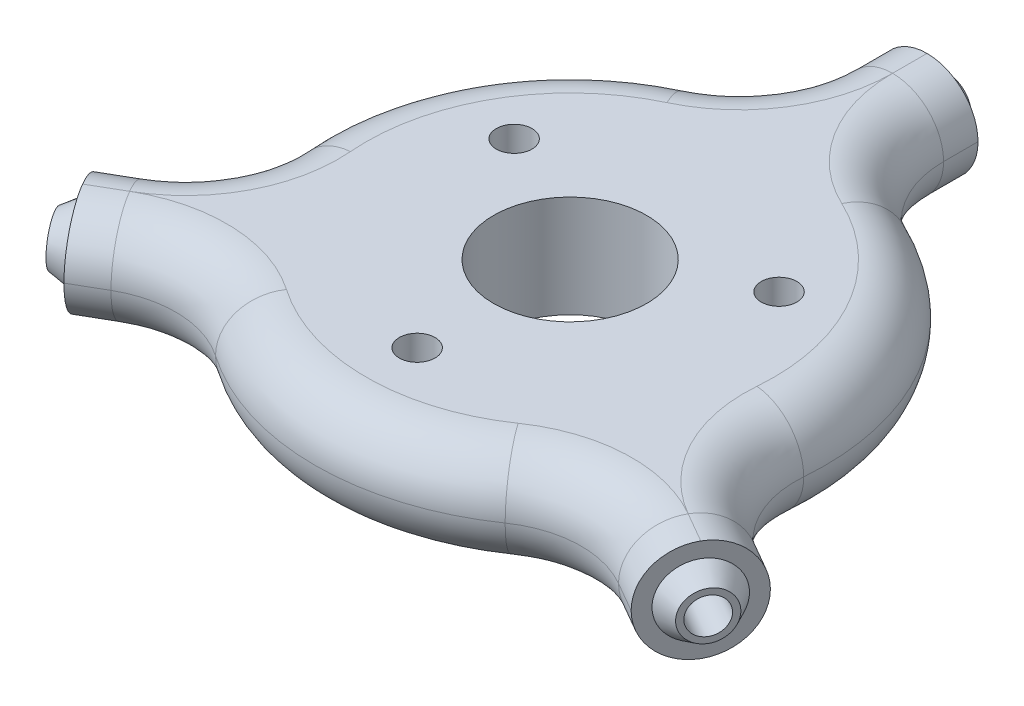
SolidWorks part; units mm, degrees
ref_plane "Front Plane" through (0, 0, 0) normal (0, 0, 1) x (1, 0, 0)
ref_plane "Top Plane" through (0, 0, 0) normal (0, 1, 0) x (1, 0, 0)
ref_plane "Right Plane" through (0, 0, 0) normal (1, 0, 0) x (0, 0, -1)
sketch "Sketch1" plane through (0, 0, 0) normal (0, 1, 0) x (1, 0, 0)
  circle A0 centre (0, 0) radius 25
  dimension "D1" = 50
extrude "Boss-Extrude1" add sketch "Sketch1" along normal mid plane 10
sketch "Sketch2" plane through (0, 5, 0) normal (0, 1, 0) x (1, 0, 0)
  line L0 (15.4904, -3.1699) -> (10.4904, -11.8301)
  line L1 (-5, 15) -> (5, 15)
  line L2 (-5, 15) -> (-5, 35)
  line L3 (-5, 35) -> (5, 35)
  line L4 (5, 15) -> (5, 35)
  line L5 (-5, 15) -> (5, 35) construction
  line L6 (-5, 35) -> (5, 15) construction
  line L7 (15.4904, -3.1699) -> (32.8109, -13.1699)
  line L8 (32.8109, -13.1699) -> (27.8109, -21.8301)
  line L9 (10.4904, -11.8301) -> (27.8109, -21.8301)
  line L10 (15.4904, -3.1699) -> (27.8109, -21.8301) construction
  line L11 (32.8109, -13.1699) -> (10.4904, -11.8301) construction
  line L12 (-10.4904, -11.8301) -> (-15.4904, -3.1699)
  line L13 (-10.4904, -11.8301) -> (-27.8109, -21.8301)
  line L14 (-27.8109, -21.8301) -> (-32.8109, -13.1699)
  line L15 (-15.4904, -3.1699) -> (-32.8109, -13.1699)
  line L16 (-10.4904, -11.8301) -> (-32.8109, -13.1699) construction
  line L17 (-27.8109, -21.8301) -> (-15.4904, -3.1699) construction
  circle A0 centre (0, 0) radius 25 construction
  point P0 (0, 25)
  point P7 (21.6506, -12.5)
  point P15 (-21.6506, -12.5)
  dimension "D1" = 10
  dimension "D2" = 35
  dimension "D3" = 3
extrude "Boss-Extrude2" add sketch "Sketch2" against normal up to surface (10 mm away) up to face at (0, -5, 25)
fillet "Fillet1" radius 10 6 edges at (23.7132, 0, 7.9173) (5, 0, -24.4949) (-5, 0, -24.4949) (-23.7132, 0, 7.9173) (18.7132, 0, 16.5776) (-18.7132, 0, 16.5776)
fillet "Fillet2" radius 5 30 edges at (-5, 5, -33.3114) (-6.5485, 5, -26.2776) (-31.3485, 5, 12.3256) (-26.0313, 5, 7.4676) (31.3485, 5, 12.3256) (26.0313, 5, 7.4676) (5, 5, -33.3114) (6.5485, 5, -26.2776) (-26.3485, 5, 20.9858) (-19.4828, 5, 18.8099) (26.3485, 5, 20.9858) (19.4828, 5, 18.8099) (-21.6506, 5, -12.5) (21.6506, 5, -12.5) (0, 5, 25) (31.3485, -5, 12.3256) (26.0313, -5, 7.4676) (5, -5, -33.3114) (6.5485, -5, -26.2776) (-26.3485, -5, 20.9858) (-19.4828, -5, 18.8099) (26.3485, -5, 20.9858) (19.4828, -5, 18.8099) (21.6506, -5, -12.5) (0, -5, 25) (-31.3485, -5, 12.3256) (-26.0313, -5, 7.4676) (-21.6506, -5, -12.5) (-5, -5, -33.3114) (-6.5485, -5, -26.2776)
sketch "Sketch3" plane through (0, 0, -35) normal (0, 0, -1) x (-1, 0, 0)
  circle A0 centre (0, 0) radius 1.75
  dimension "D1" = 3.5
extrude "Cut-Extrude1" cut sketch "Sketch3" against normal blind 20
sketch "Sketch4" plane through (0, -5, 0) normal (0, -1, 0) x (1, 0, 0)
  line L1 (-2.85, -21.5) -> (2.85, -21.5)
  line L2 (-2.85, -21.5) -> (-2.85, -18.5)
  line L3 (-2.85, -18.5) -> (2.85, -18.5)
  line L4 (2.85, -21.5) -> (2.85, -18.5)
  line L5 (-2.85, -21.5) -> (2.85, -18.5) construction
  line L6 (-2.85, -18.5) -> (2.85, -21.5) construction
  point P0 (0, -20)
  dimension "D1" = 5.7
  dimension "D2" = 20
  dimension "D3" = 3
extrude "Cut-Extrude2" cut sketch "Sketch4" against normal blind 8
pattern_circular "CirPattern1" count 3 over 360 about axis through (0, 0, 0) along (0, -1, 0) of "Cut-Extrude1", "Cut-Extrude2"
sketch "Sketch5" plane through (0, 5, 0) normal (0, 1, 0) x (1, 0, 0)
  line L0 (0, 38.428) -> (0, 0) construction
  line L1 (0, 0) -> (-46.2293, 26.6905) construction
  circle A0 centre (-12.9904, 7.5) radius 1.75
  circle A1 centre (12.9904, 7.5) radius 1.75
  circle A2 centre (0, -15) radius 1.75
  dimension "D2" = 3.5
  dimension "D3" = 15
  dimension "D1" = 60
  dimension "D4" = 3
extrude "Cut-Extrude3" cut sketch "Sketch5" against normal through all
sketch "Sketch7" plane through (0, 5, 0) normal (0, 1, 0) x (1, 0, 0)
  circle A0 centre (0, 0) radius 7.5
  dimension "D1" = 15
extrude "Cut-Extrude5" cut sketch "Sketch7" against normal through all
sketch "Sketch8" plane through (30.3109, 0, 17.5) normal (0.866, 0, 0.5) x (0.5, 0, -0.866)
  circle A0 centre (0, 0) radius 3.5
  dimension "D1" = 7
extrude "Boss-Extrude3" add sketch "Sketch8" along normal blind 2
chamfer "Chamfer1" distance 2 angle 30 1 edges at (33.7929, 0, 15.4689) first distance on face at (33.7929, 0, 15.4689)
sketch "Sketch9" plane through (32.0429, 0, 18.5) normal (0.866, 0, 0.5) x (0.5, 0, -0.866)
  circle A0 centre (0, 0) radius 1.75
  dimension "D1" = 3.5
extrude "Cut-Extrude6" cut sketch "Sketch9" against normal blind 2
pattern_circular "CirPattern2" count 3 over 360 about axis through (0, 0, 0) along (0, -1, 0) of "Chamfer1", "Boss-Extrude3"
sketch "Sketch10" plane through (-32.0429, 0, 18.5) normal (-0.866, 0, 0.5) x (0.5, 0, 0.866)
  circle A0 centre (0, 0) radius 1.75
  dimension "D1" = 3.5
extrude "Cut-Extrude7" cut sketch "Sketch10" against normal blind 2
sketch "Sketch11" plane through (0, 0, -37) normal (0, 0, -1) x (-1, 0, 0)
  circle A0 centre (0, 0) radius 1.75
  dimension "D1" = 3.5
extrude "Cut-Extrude8" cut sketch "Sketch11" against normal blind 2 contours A0
sketch "Sketch12" plane through (0, -5, 0) normal (0, -1, 0) x (1, 0, 0)
  line L0 (17.4465, 6.7818) -> (20.0445, 8.2818) construction
  line L1 (12.9904, -10.7909) -> (15.8404, -9.1454)
  line L2 (15.8404, -9.1454) -> (15.8404, -5.8546)
  line L3 (15.8404, -5.8546) -> (12.9904, -4.2091)
  line L4 (12.9904, -4.2091) -> (10.1404, -5.8546)
  line L5 (10.1404, -5.8546) -> (10.1404, -9.1454)
  line L6 (10.1404, -9.1454) -> (12.9904, -10.7909)
  line L7 (-15.8404, -5.8546) -> (-15.8404, -9.1454)
  line L8 (-15.8404, -9.1454) -> (-12.9904, -10.7909)
  line L9 (-12.9904, -10.7909) -> (-10.1404, -9.1454)
  line L10 (-10.1404, -9.1454) -> (-10.1404, -5.8546)
  line L11 (-10.1404, -5.8546) -> (-12.9904, -4.2091)
  line L12 (-12.9904, -4.2091) -> (-15.8404, -5.8546)
  line L13 (2.85, 16.6454) -> (0, 18.2909)
  line L14 (0, 18.2909) -> (-2.85, 16.6454)
  line L15 (-2.85, 16.6454) -> (-2.85, 13.3546)
  line L16 (-2.85, 13.3546) -> (0, 11.7091)
  line L17 (0, 11.7091) -> (2.85, 13.3546)
  line L18 (2.85, 13.3546) -> (2.85, 16.6454)
  circle A0 centre (12.9904, -7.5) radius 2.85 construction
  circle A1 centre (12.9904, -7.5) radius 1.75 construction
  circle A2 centre (0, 15) radius 1.75 construction
  point P12 (-1.425, 12.5318)
  dimension "D1" = 5.7
  dimension "D3" = 5.7
  dimension "D4" = 5.7
  dimension "D5" = 5.7
  dimension "D6" = 2.85
  dimension "D7" = 2.85
  dimension "D2" = 3
extrude "Cut-Extrude9" cut sketch "Sketch12" against normal blind 3
